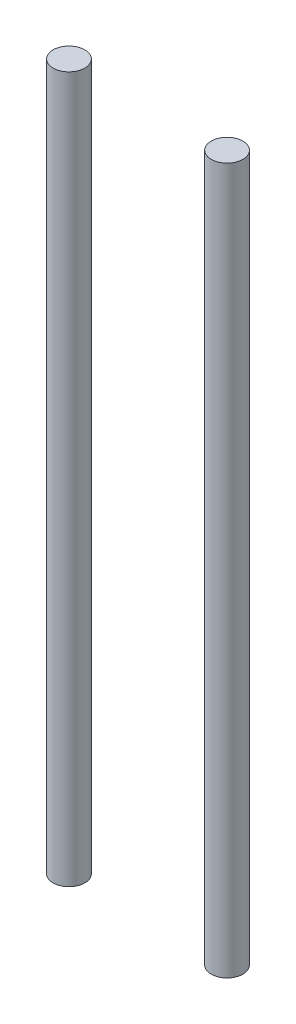
SolidWorks part; units mm, degrees
ref_plane "Front Plane" through (0, 0, 0) normal (0, 0, 1) x (1, 0, 0)
ref_plane "Top Plane" through (0, 0, 0) normal (0, 1, 0) x (1, 0, 0)
ref_plane "Right Plane" through (0, 0, 0) normal (1, 0, 0) x (0, 0, -1)
sketch "Sketch1" plane through (0, 0, 0) normal (0, 0, 1) x (1, 0, 0)
  line L0 (0, 262.7825) -> (0, 125) construction
  line L1 (-200.2495, 0) -> (418.6194, 0) construction
  line L2 (-55, -105) -> (-55, 105)
  line L4 (-75, -125) -> (-75, 125)
  line L6 (75, -125) -> (75, 125)
  line L7 (-75, -125) -> (75, 125) construction
  line L8 (-75, 125) -> (75, -125) construction
  line L10 (55, -105) -> (55, 105)
  line L12 (55, 105) -> (55, 125)
  line L13 (-55, 105) -> (-55, 125)
  line L14 (-55, -105) -> (-55, -125)
  line L15 (55, -105) -> (55, -125)
  line L16 (-55, -105) -> (55, -105) construction
  line L17 (0, -125) -> (0, -394.6857) construction
  line L18 (-55, 105) -> (55, 105) construction
  line L19 (0, 0) -> (0, -105) construction
  line L21 (-75, 125) -> (75, 125) construction
  line L23 (-75, -125) -> (75, -125) construction
  line L24 (-63.3569, 130) -> (-75, 130)
  line L25 (55, 125) -> (-55, 125)
  line L26 (75, 125) -> (75, 130)
  line L27 (75, 130) -> (-63.3569, 130)
  line L28 (-75, 125) -> (-75, 130)
  line L30 (55, -125) -> (-55, -125)
  line L31 (75, -125) -> (75, -130)
  line L32 (75, -130) -> (-75, -130)
  line L33 (-75, -125) -> (-75, -130)
  point P5 (0, 0)
  dimension "D1" = 250
  dimension "D2" = 150
  dimension "D4" = 5
  dimension "D3" = 210
  dimension "D5" = 5
extrude "Boss-Extrude1" add sketch "Sketch1" along normal blind 20
sketch "Sketch2" plane through (0, -130, 0) normal (0, -1, 0) x (1, 0, 0)
  line L0 (0, 0) -> (0, 33.0381) construction
  line L1 (-75, 0) -> (75, 0) construction
  line L2 (-75, 20) -> (-75, 0) construction
  circle A0 centre (-28, 10) radius 5.6125
  circle A1 centre (28, 10) radius 5.6125
  dimension "D1" = 47
extrude "Boss-Extrude2" add sketch "Sketch2" against normal blind 262
sketch "Sketch3" plane through (0, 125, 0) normal (0, -1, 0) x (1, 0, 0)
  circle A0 centre (-44.25, 10) radius 3.25
  circle A1 centre (-11.75, 10) radius 3.25
  circle A2 centre (11.75, 10) radius 3.25
  circle A3 centre (44.25, 10) radius 3.25
extrude "Cut-Extrude1" cut sketch "Sketch3" against normal blind 10
sketch "Sketch4" plane through (0, -130, 0) normal (0, -1, 0) x (1, 0, 0)
  circle A0 centre (-44.25, 10) radius 3.25
  circle A1 centre (-11.75, 10) radius 3.25
  circle A2 centre (11.75, 10) radius 3.25
  circle A3 centre (44.25, 10) radius 3.25
extrude "Cut-Extrude2" cut sketch "Sketch4" against normal blind 10
sketch "Sketch5" plane through (0, 0, 0) normal (0, 0, -1) x (-1, 0, 0)
  line L0 (-75, -130) -> (-75, 130) construction
  line L1 (-75, 125) -> (75, 125)
  line L2 (-75, 125) -> (-75, -125)
  line L3 (-75, -125) -> (75, -125)
  line L4 (75, 125) -> (75, -125)
  line L5 (75, 130) -> (75, -130) construction
  line L8 (75, -130) -> (-75, -130) construction
  dimension "D1" = 5
extrude "Cut-Extrude4" cut sketch "Sketch5" against normal through all both and the other way through all flip side to cut
sketch "Sketch7" plane through (0, -125, 0) normal (0, -1, 0) x (1, 0, 0)
  line L1 (-123.3958, 56.4575) -> (-42.2878, 56.4575)
  line L2 (-123.3958, 56.4575) -> (-123.3958, -9.2171)
  line L3 (-123.3958, -9.2171) -> (-42.2878, -9.2171)
  line L4 (-42.2878, 56.4575) -> (-42.2878, -9.2171)
  line L5 (38.4919, 44.3077) -> (92.3565, 44.3077)
  line L6 (38.4919, 44.3077) -> (38.4919, -16.4413)
  line L7 (38.4919, -16.4413) -> (92.3565, -16.4413)
  line L8 (92.3565, 44.3077) -> (92.3565, -16.4413)
extrude "Cut-Extrude5" cut sketch "Sketch7" against normal through all both and the other way through all
